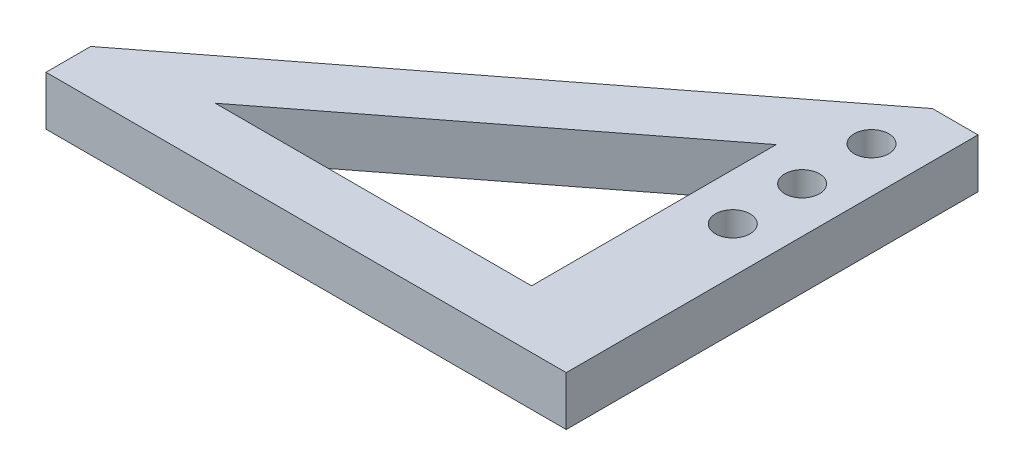
SolidWorks part; units mm, degrees
material "Delrin 2700 NC010, Low Viscosity Acetal Copolymer (SS)"
ref_plane "Front Plane" through (0, 0, 0) normal (0, 0, 1) x (1, 0, 0)
ref_plane "Top Plane" through (0, 0, 0) normal (0, 1, 0) x (1, 0, 0)
ref_plane "Right Plane" through (0, 0, 0) normal (1, 0, 0) x (0, 0, -1)
sketch "Sketch1" plane through (0, 0, 0) normal (0, 1, 0) x (1, 0, 0)
  line L0 (1.905, 1.4732) -> (17.5479, 13.5703)
  line L1 (1.905, 0) -> (19.05, 0)
  line L2 (5.5774, 1.905) -> (16.002, 1.905)
  line L3 (16.002, 1.905) -> (16.002, 9.9667)
  line L4 (19.05, 0) -> (19.05, 13.5703)
  line L5 (5.5774, 1.905) -> (16.002, 9.9667)
  line L6 (17.145, 1.905) -> (17.145, 10.8506) construction
  line L7 (5.5774, 1.905) -> (17.145, 10.8506) construction
  line L8 (5.5774, 1.905) -> (17.145, 1.905) construction
  line L9 (17.5479, 13.5703) -> (19.05, 13.5703)
  line L10 (19.05, 0) -> (19.05, 14.732) construction
  line L11 (0, 0) -> (19.05, 14.732) construction
  line L12 (1.905, 0) -> (1.905, 1.4732)
  line L13 (0, 0) -> (19.05, 0) construction
  circle A0 centre (17.5479, 11.5622) radius 0.5715
  circle A3 centre (17.5479, 9.2762) radius 0.5715
  circle A4 centre (17.5479, 6.9902) radius 0.5715
  dimension "D5" = 1.143
  dimension "D6" = 3
  dimension "D1" = 17.145
  dimension "D2" = 13.5703
  dimension "D4" = 3.048
  dimension "D3" = 1.905
extrude "Boss-Extrude1" add sketch "Sketch1" along normal blind 1.6256
